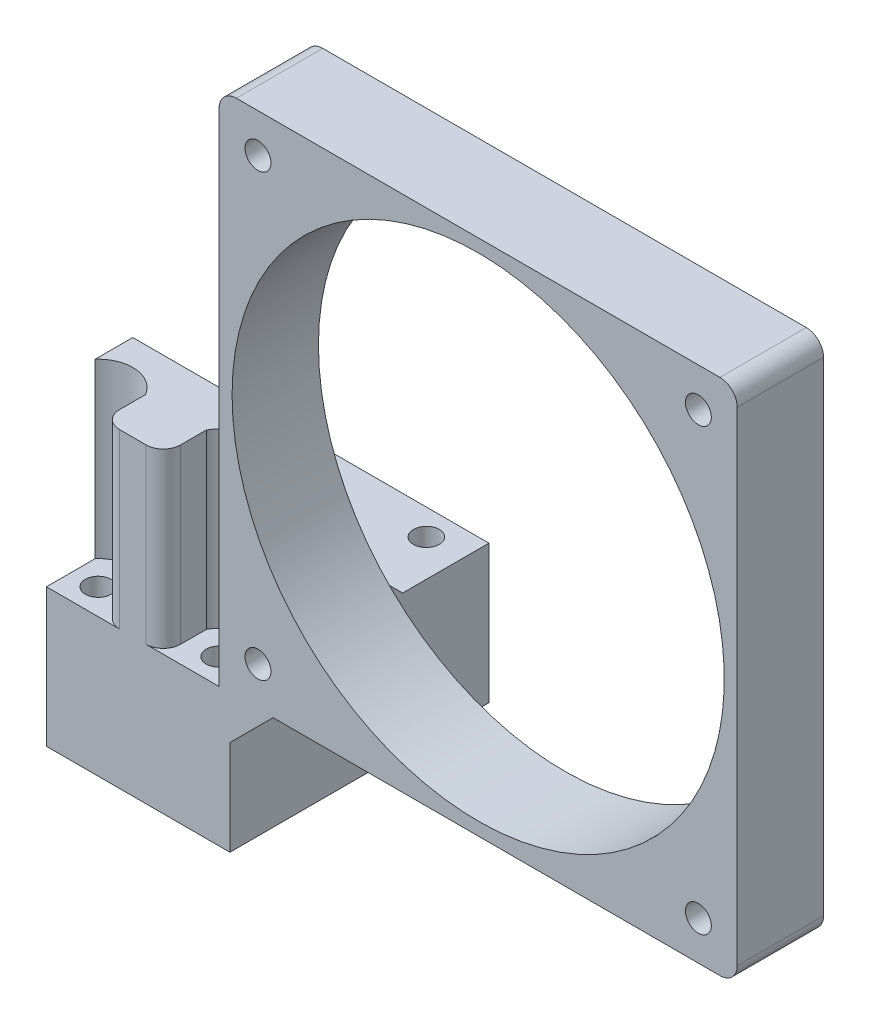
SolidWorks part; units mm, degrees
ref_plane "前视基准面" through (0, 0, 0) normal (0, 0, 1) x (1, 0, 0)
ref_plane "上视基准面" through (0, 0, 0) normal (0, 1, 0) x (1, 0, 0)
ref_plane "右视基准面" through (0, 0, 0) normal (1, 0, 0) x (0, 0, -1)
other "Configuration Table"
sketch "草图1" plane through (0, 0, 0) normal (0, 0, 1) x (1, 0, 0)
  line L1 (0, 0) -> (-60, 0)
  line L2 (0, 0) -> (0, 60)
  line L3 (0, 60) -> (-60, 60)
  line L4 (-60, 0) -> (-60, 60)
  dimension "D1" = 60
  dimension "D2" = 60
extrude "凸台-拉伸1" add sketch "草图1" along normal blind 5
sketch "草图2" plane through (0, 0, 0) normal (0, 0, -1) x (-1, 0, 0)
  line L0 (0, 0) -> (0, 60) construction
  line L1 (0, 60) -> (60, 60) construction
  circle A0 centre (4.5, 55.5) radius 1.5
  circle A1 centre (55.5, 55.5) radius 1.5
  circle A2 centre (4.5, 4.5) radius 1.5
  circle A3 centre (55.5, 4.5) radius 1.5
  dimension "D1" = 51
  dimension "D2" = 51
  dimension "D3" = 51
  dimension "D4" = 51
  dimension "D5" = 4.5
  dimension "D6" = 4.5
  dimension "D7" = 4.5
  dimension "D8" = 4.5
  dimension "D9" = 3
extrude "切除-拉伸1" cut sketch "草图2" against normal blind 5
sketch "草图3" plane through (0, 0, 0) normal (0, 0, -1) x (-1, 0, 0)
  line L0 (30, 60) -> (30, -2.4653) construction
  line L5 (0, 60) -> (60, 60) construction
  line L6 (0, 30) -> (70.1164, 30) construction
  line L7 (0, 0) -> (0, 60) construction
  circle A2 centre (30, 30) radius 28.5
  dimension "D1" = 57
extrude "切除-拉伸2" cut sketch "草图3" against normal blind 5
sketch "草图4" plane through (-60, 0, 0) normal (-1, 0, 0) x (0, 0, 1)
  line L1 (0, 0) -> (5, 0)
  line L2 (0, 0) -> (0, 20)
  line L3 (0, 20) -> (5, 20)
  line L4 (5, 0) -> (5, 20)
  dimension "D1" = 20
extrude "凸台-拉伸2" add sketch "草图4" along normal blind 20
sketch "草图5" plane through (0, 0, 0) normal (0, -1, 0) x (1, 0, 0)
  line L1 (-80, 10) -> (-58.75, 10)
  line L2 (-80, 10) -> (-80, -20)
  line L3 (-80, -20) -> (-58.75, -20)
  line L4 (-58.75, 10) -> (-58.75, -20)
  line L5 (-80, 0) -> (-80, 5) construction
  line L6 (-80, 0) -> (0, 0) construction
  dimension "D1" = 21.25
  dimension "D2" = 20
  dimension "D3" = 30
  dimension "D4" = 0
extrude "凸台-拉伸3" add sketch "草图5" along normal blind 16
sketch "草图6" plane through (0, -16, 0) normal (0, -1, 0) x (1, 0, 0)
  line L0 (-58.75, 10) -> (-80, 10) construction
  line L1 (-80, 10) -> (-80, -20) construction
  line L3 (-80, -20) -> (-58.75, -20) construction
  circle A0 centre (-77, 7) radius 1.5
  circle A1 centre (-63, 7) radius 1.5
  circle A2 centre (-77, -17) radius 1.5
  circle A3 centre (-63, -17) radius 1.5
  dimension "D1" = 3
  dimension "D2" = 3
  dimension "D3" = 14
  dimension "D4" = 14
  dimension "D7" = 3
  dimension "D8" = 3
  dimension "D9" = 3
extrude "切除-拉伸3" cut sketch "草图6" against normal blind 30
sketch "草图7" plane through (0, 0, 0) normal (0, 1, 0) x (1, 0, 0)
  circle A2 centre (-77, -7) radius 4
  circle A3 centre (-63, -7) radius 4
  dimension "D1" = 8
  dimension "D2" = 8
extrude "切除-拉伸4" cut sketch "草图7" along normal blind 30
chamfer "倒角1" distance 10 angle 45 1 edges at (-69.375, 0, 0)
fillet "圆角1" radius 2 3 edges at (0, 0, 2.5) (-60, 60, 2.5) (0, 60, 2.5)
sketch "草图8" plane through (0, 0, 5) normal (0, 0, 1) x (1, 0, 0)
  line L7 (-58.75, 0) -> (-2, 0)
  line L8 (0, 2) -> (0, 58)
  line L9 (-2, 60) -> (-58, 60)
  line L10 (-60, 58) -> (-60, 30)
  line L11 (-60, 30) -> (-59.5359, 30)
  line L12 (-59.5359, 30) -> (-59.5359, 0)
  line L13 (-59.5359, 0) -> (-58.75, 0)
  line L14 (-58.75, 0) -> (-2, 0)
  line L15 (0, 2) -> (0, 58)
  line L16 (-2, 60) -> (-58, 60)
  line L17 (-60, 58) -> (-60, 30)
  line L19 (-59.5359, 30) -> (-59.5359, 0)
  line L20 (-59.5359, 0) -> (-58.75, 0)
  line L21 (-60, 30) -> (-59.5359, 30)
  arc A3 (-2, 0) -> (0, 2) centre (-2, 2) ccw
  arc A4 (0, 58) -> (-2, 60) centre (-2, 58) ccw
  arc A5 (-58, 60) -> (-60, 58) centre (-58, 58) ccw
  arc A6 (-2, 0) -> (0, 2) centre (-2, 2) ccw
  arc A7 (0, 58) -> (-2, 60) centre (-2, 58) ccw
  arc A8 (-58, 60) -> (-60, 58) centre (-58, 58) ccw
  dimension "D1" = 0
extrude "凸台-拉伸4" add sketch "草图8" along normal up to surface (5 mm away) up to face at (-69.375, -8, 10)
sketch "草图9" plane through (0, 0, 5) normal (0, 0, -1) x (-1, 0, 0)
  circle A0 centre (4.5, 4.5) radius 1.5 construction
  circle A1 centre (55.5, 4.5) radius 1.5 construction
  circle A2 centre (55.5, 55.5) radius 1.5 construction
  circle A3 centre (4.5, 55.5) radius 1.5 construction
  circle A4 centre (30, 30) radius 28.5 construction
  circle A5 centre (4.5, 4.5) radius 1.5
  circle A6 centre (55.5, 4.5) radius 1.5
  circle A7 centre (55.5, 55.5) radius 1.5
  circle A8 centre (4.5, 55.5) radius 1.5
  circle A9 centre (30, 30) radius 28.5
extrude "切除-拉伸5" cut sketch "草图9" against normal up to surface (5 mm away) up to face at (-44.4737, 20.4934, 10)
sketch "草图11" plane through (0, 0, 5) normal (0, 0, 1) x (1, 0, 0)
  line L4 (-66.4641, 20) -> (-73.5359, 20)
  line L5 (-73.5359, 20) -> (-73.5359, 0)
  line L6 (-73.5359, 0) -> (-66.4641, 0)
  line L7 (-66.4641, 0) -> (-66.4641, 20)
  line L8 (-66.4641, 20) -> (-73.5359, 20)
  line L9 (-73.5359, 20) -> (-73.5359, 0)
  line L10 (-73.5359, 0) -> (-66.4641, 0)
  line L11 (-66.4641, 0) -> (-66.4641, 20)
  dimension "D1" = 0
extrude "凸台-拉伸5" add sketch "草图11" along normal up to surface (5 mm away) up to face at (-57, 4.5, 10)
fillet "圆角2" radius 2 2 edges at (-66.4641, 10, 10) (-73.5359, 10, 10)
chamfer "倒角2" distance 5 angle 45 1 edges at (-58.75, 0, 5)
sketch "草图12" plane through (0, 30, 0) normal (0, -1, 0) x (1, 0, 0)
  line L3 (-59.5359, 5) -> (-59.5359, 10)
  line L4 (-59.5359, 10) -> (-60, 10)
  line L5 (-60, 10) -> (-60, 4.3542)
  line L6 (-59.5359, 5) -> (-59.5359, 10)
  line L7 (-59.5359, 10) -> (-60, 10)
  line L8 (-60, 10) -> (-60, 4.3542)
  arc A1 (-60, 4.3542) -> (-59.5359, 5) centre (-63, 7) ccw
  arc A2 (-60, 4.3542) -> (-59.5359, 5) centre (-63, 7) ccw
  dimension "D1" = 0
extrude "凸台-拉伸6" add sketch "草图12" along normal up to surface (30 mm away) up to face at (-77, 0, 5.5)
